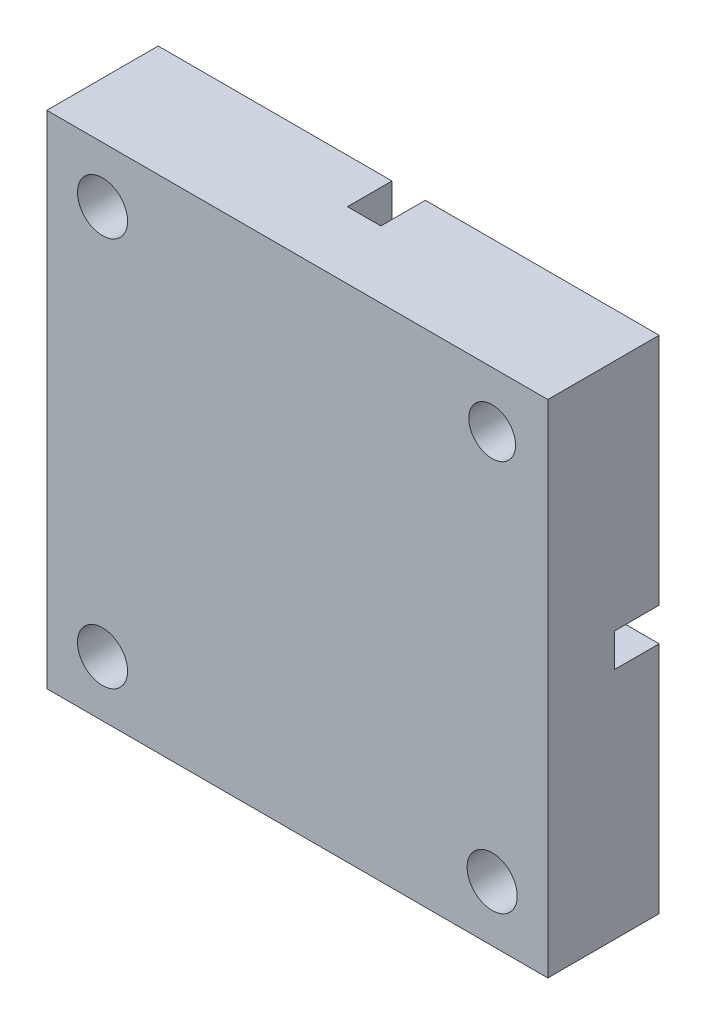
SolidWorks part; units mm, degrees
ref_plane "Front Plane" through (0, 0, 0) normal (0, 0, 1) x (1, 0, 0)
ref_plane "Top Plane" through (0, 0, 0) normal (0, 1, 0) x (1, 0, 0)
ref_plane "Right Plane" through (0, 0, 0) normal (1, 0, 0) x (0, 0, -1)
sketch "Sketch1" plane through (0, 0, 0) normal (0, 0, 1) x (1, 0, 0)
  line L1 (0, 0) -> (45, 0)
  line L2 (0, 0) -> (0, 45)
  line L3 (0, 45) -> (45, 45)
  line L4 (45, 0) -> (45, 45)
  line L5 (5, 5) -> (40, 5) construction
  line L6 (5, 5) -> (5, 40) construction
  line L7 (5, 40) -> (40, 40) construction
  line L8 (40, 5) -> (40, 40) construction
  line L9 (5, 5) -> (40, 40) construction
  line L10 (5, 40) -> (40, 5) construction
  line L11 (8.1754, 40) -> (6.5877, 42.75) construction
  line L12 (6.5877, 42.75) -> (3.4123, 42.75) construction
  line L13 (3.4123, 42.75) -> (1.8246, 40) construction
  line L14 (1.8246, 40) -> (3.4123, 37.25) construction
  line L15 (3.4123, 37.25) -> (6.5877, 37.25) construction
  line L16 (6.5877, 37.25) -> (8.1754, 40) construction
  circle A0 centre (5, 5) radius 2.25
  circle A1 centre (5, 40) radius 2.25
  circle A2 centre (40, 40) radius 2.1
  circle A3 centre (40, 5) radius 2.25
  circle A4 centre (5, 40) radius 2.75 construction
  point P10 (22.5, 22.5)
  dimension "D3" = 4.5
  dimension "D4" = 4.5
  dimension "D5" = 4.2
  dimension "D6" = 4.5
  dimension "D1" = 45
  dimension "D2" = 45
  dimension "D7" = 5
  dimension "D8" = 5
  dimension "D9" = 5
  dimension "D10" = 5
  dimension "D11" = 5.5
extrude "Boss-Extrude1" add sketch "Sketch1" along normal blind 10
sketch "Sketch2" plane through (0, 0, 0) normal (0, 0, 1) x (1, 0, 0)
  line L1 (8.7528, 5) -> (6.8764, 8.25)
  line L2 (6.8764, 8.25) -> (3.1236, 8.25)
  line L3 (3.1236, 8.25) -> (1.2472, 5)
  line L4 (1.2472, 5) -> (3.1236, 1.75)
  line L5 (3.1236, 1.75) -> (6.8764, 1.75)
  line L6 (6.8764, 1.75) -> (8.7528, 5)
  line L7 (8.7528, 40) -> (6.8764, 43.25)
  line L8 (6.8764, 43.25) -> (3.1236, 43.25)
  line L9 (3.1236, 43.25) -> (1.2472, 40)
  line L10 (1.2472, 40) -> (3.1236, 36.75)
  line L11 (3.1236, 36.75) -> (6.8764, 36.75)
  line L12 (6.8764, 36.75) -> (8.7528, 40)
  line L13 (43.7528, 40) -> (41.8764, 43.25)
  line L14 (41.8764, 43.25) -> (38.1236, 43.25)
  line L15 (38.1236, 43.25) -> (36.2472, 40)
  line L16 (36.2472, 40) -> (38.1236, 36.75)
  line L17 (38.1236, 36.75) -> (41.8764, 36.75)
  line L18 (41.8764, 36.75) -> (43.7528, 40)
  line L19 (43.7528, 5) -> (41.8764, 8.25)
  line L20 (41.8764, 8.25) -> (38.1236, 8.25)
  line L21 (38.1236, 8.25) -> (36.2472, 5)
  line L22 (36.2472, 5) -> (38.1236, 1.75)
  line L23 (38.1236, 1.75) -> (41.8764, 1.75)
  line L24 (41.8764, 1.75) -> (43.7528, 5)
  circle A0 centre (5, 5) radius 3.25 construction
  circle A1 centre (5, 40) radius 3.25 construction
  circle A2 centre (40, 40) radius 3.25 construction
  circle A3 centre (40, 5) radius 3.25 construction
  dimension "D1" = 6.5
  dimension "D2" = 6.5
  dimension "D3" = 6.5
  dimension "D4" = 6.5
extrude "Cut-Extrude1" cut sketch "Sketch2" along normal blind 5
sketch "Sketch3" plane through (0, 0, 0) normal (0, 0, -1) x (-1, 0, 0)
  line L0 (-45, 24) -> (-24, 24)
  line L1 (-45, 0) -> (-45, 45) construction
  line L2 (-24, 24) -> (-24, 45)
  line L3 (-45, 45) -> (0, 45) construction
  line L4 (-24, 45) -> (-21, 45)
  line L5 (-21, 45) -> (-21, 24)
  line L6 (-21, 24) -> (0, 24)
  line L7 (0, 45) -> (0, 0) construction
  line L8 (0, 24) -> (0, 21)
  line L9 (0, 21) -> (-21, 21)
  line L10 (-21, 21) -> (-21, 0)
  line L11 (0, 0) -> (-45, 0) construction
  line L12 (-21, 0) -> (-24, 0)
  line L13 (-24, 0) -> (-24, 21)
  line L14 (-24, 21) -> (-45, 21)
  line L15 (-45, 21) -> (-45, 24)
  point P12 (-22.5, 0)
  point P21 (-22.5, 0)
  point P22 (-45, 22.5)
  point P24 (-45, 22.5)
  dimension "D1" = 3
  dimension "D2" = 3
extrude "Cut-Extrude2" cut sketch "Sketch3" against normal blind 4
